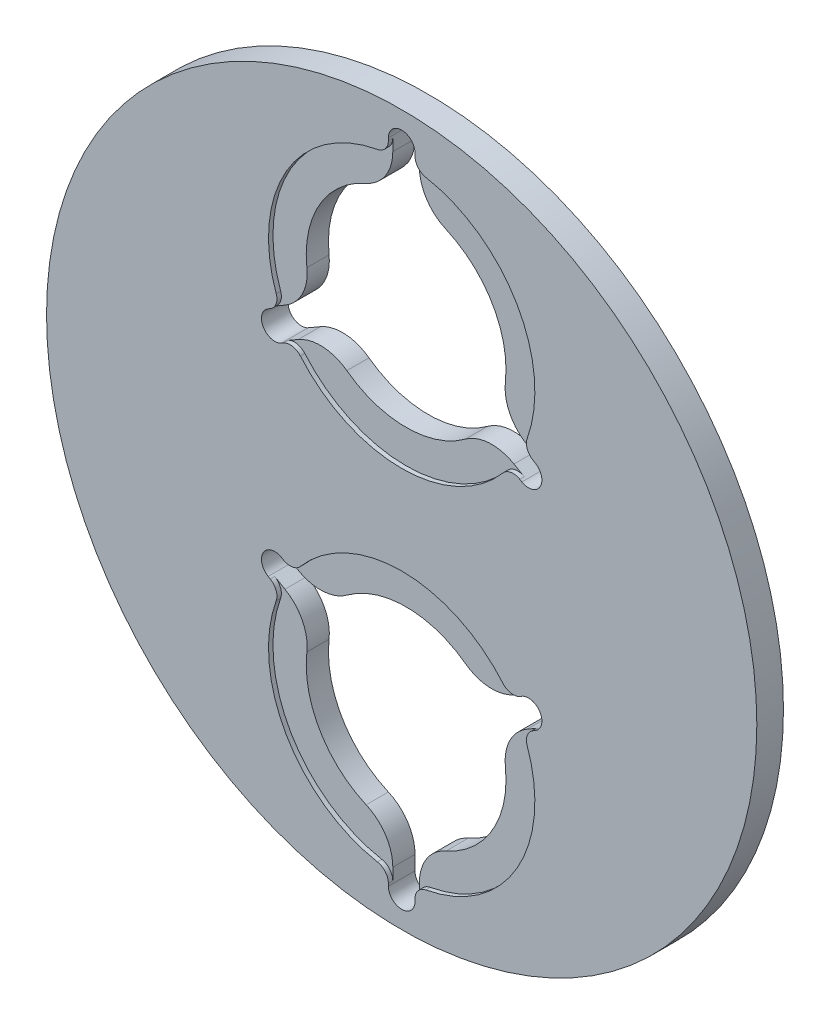
SolidWorks part; units mm, degrees
material "Plain Carbon Steel"
ref_plane "Front Plane" through (0, 0, 0) normal (0, 0, 1) x (1, 0, 0)
ref_plane "Top Plane" through (0, 0, 0) normal (0, 1, 0) x (1, 0, 0)
ref_plane "Right Plane" through (0, 0, 0) normal (1, 0, 0) x (0, 0, -1)
sketch "Sketch2" plane through (0, 0, 0) normal (0, 0, 1) x (1, 0, 0)
  circle A0 centre (0, 0) radius 80
  dimension "D1" = 160
extrude "Boss-Extrude1" add sketch "Sketch2" along normal blind 6
sketch "Sketch1" plane through (0, 0, 0) normal (0, 0, 1) x (1, 0, 0)
  line L0 (0, 80) -> (0, -80) construction
  line L1 (0, 40) -> (25.9808, 25) construction
  line L2 (0, 40) -> (-25.9808, 25) construction
  line L3 (25.9808, 25) -> (28.5788, 23.5) construction
  line L4 (-25.9808, 25) -> (-28.5788, 23.5) construction
  line L5 (3, 73) -> (3, 69.8496)
  line L6 (-3, 73) -> (-3, 69.8496)
  line L7 (28.5788, 23.5) -> (30.0788, 26.0981) construction
  line L8 (30.0788, 26.0981) -> (27.3505, 27.6733)
  line L9 (28.5788, 23.5) -> (27.0788, 20.9019) construction
  line L10 (27.0788, 20.9019) -> (24.3505, 22.4771)
  line L11 (-28.5788, 23.5) -> (-30.0788, 26.0981) construction
  line L12 (-30.0788, 26.0981) -> (-27.3505, 27.6733)
  line L13 (-28.5788, 23.5) -> (-27.0788, 20.9019) construction
  line L14 (-27.0788, 20.9019) -> (-24.3505, 22.4771)
  line L15 (27.3505, 27.6733) -> (20.8116, 31.4485)
  line L16 (24.3505, 22.4771) -> (17.8116, 26.2524)
  line L17 (-24.3505, 22.4771) -> (-17.8116, 26.2524)
  line L18 (-27.3505, 27.6733) -> (-20.8116, 31.4485)
  line L19 (-3, 69.8496) -> (-3, 62.2991)
  line L20 (3, 69.8496) -> (3, 62.2991)
  circle A0 centre (0, 0) radius 80
  circle A1 centre (0, 40) radius 30
  circle A2 centre (0, 40) radius 22.5
  circle A3 centre (0, 73) radius 3
  circle A4 centre (-28.5788, 23.5) radius 3
  circle A5 centre (28.5788, 23.5) radius 3
  dimension "D1" = 160
  dimension "D2" = 60
  dimension "D4" = 45
  dimension "D7" = 6
  dimension "D3" = 40
  dimension "D5" = 120
  dimension "D6" = 120
extrude "Cut-Extrude2" cut sketch "Sketch1" along normal blind 6 contours A2 | A2 L16 A1 L15 | A2 L18 A1 L17 | A2 L20 A1 L19 | A4 L14 A1 | A4 A1 L12 | A4 | A5 L8 A1 | A5 A1 L10 | A5 | A3 A1 L5 | A3 | A3 L6 A1 | A5 region at (0, 73, 0) region at (2.3242, 70.6185, 0) region at (0, 66.1914, 0) region at (-2.3242, 70.6185, 0) region at (0, 40, 0) region at (22.6824, 26.9043, 0) region at (27.6785, 26.7035, 0) region at (-27.6785, 26.7035, 0) region at (-22.6824, 26.9043, 0) region at (28.5788, 23.5, 0) region at (25.3543, 22.678, 0) region at (-28.5788, 23.5, 0) region at (-25.3543, 22.678, 0)
sketch "Sketch3" plane through (0, 0, 6) normal (0, 0, 1) x (1, 0, 0)
  circle A0 centre (0, 40) radius 30
  arc A1 (-3, 62.2991) -> (-20.8116, 31.4485) centre (0, 40) ccw construction
  dimension "D1" = 60
extrude "Cut-Extrude3" cut sketch "Sketch3" against normal blind 1
ref_axis "Axis1" through (0, 0, 6) along (0, 0, -1)
fillet "Fillet1" radius 3 6 edges at (24.3505, 22.4771, 5.5) (-24.3505, 22.4771, 5.5) (-27.3505, 27.6733, 5.5) (-3, 69.8496, 5.5) (27.3505, 27.6733, 5.5) (3, 69.8496, 5.5)
fillet "Fillet2" radius 10 6 edges at (-3, 62.2991, 2.5) (-20.8116, 31.4485, 2.5) (-17.8116, 26.2524, 2.5) (17.8116, 26.2524, 2.5) (20.8116, 31.4485, 2.5) (3, 62.2991, 2.5)
pattern_circular "CirPattern1" count 2 over 360 about axis through (0, 0, 6) along (0, 0, -1) of "Cut-Extrude2", "Cut-Extrude3", "Fillet1", "Fillet2"
